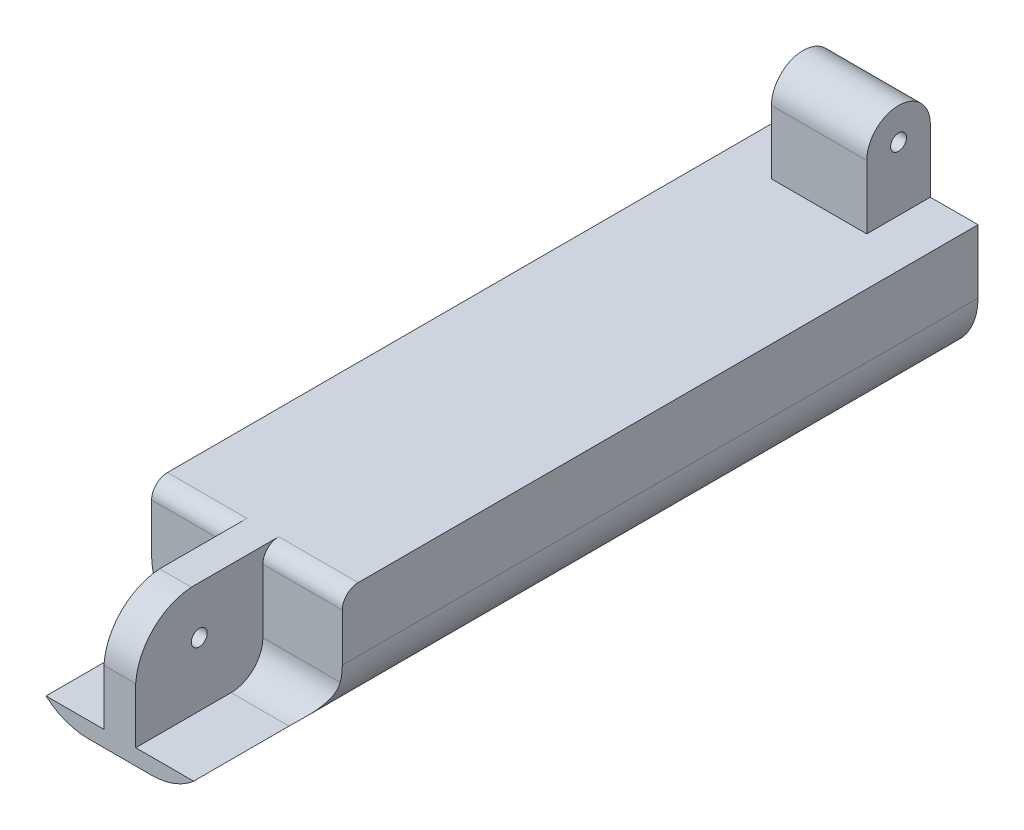
SolidWorks part; units mm, degrees
material "PVC 0.007 Plasticized"
ref_plane "Front Plane" through (0, 0, 0) normal (0, 0, 1) x (1, 0, 0)
ref_plane "Top Plane" through (0, 0, 0) normal (0, 1, 0) x (1, 0, 0)
ref_plane "Right Plane" through (0, 0, 0) normal (1, 0, 0) x (0, 0, -1)
sketch "Sketch1" plane through (0, 0, 0) normal (0, 0, 1) x (1, 0, 0)
  line L1 (0, 0) -> (-60, 0)
  line L2 (0, 0) -> (0, 40)
  line L3 (0, 40) -> (-60, 40)
  line L4 (-60, 0) -> (-60, 40)
  dimension "D1" = 60
  dimension "D2" = 40
extrude "Boss-Extrude1" add sketch "Sketch1" along normal blind 240
sketch "Sketch2" plane through (0, 40, 0) normal (0, 1, 0) x (1, 0, 0)
  line L1 (-60, -240) -> (-35, -240)
  line L2 (-60, -240) -> (-60, -200)
  line L3 (-60, -200) -> (-35, -200)
  line L4 (-35, -240) -> (-35, -200)
  line L5 (0, -240) -> (-25, -240)
  line L6 (0, -240) -> (0, -200)
  line L7 (0, -200) -> (-25, -200)
  line L8 (-25, -240) -> (-25, -200)
  dimension "D1" = 25
  dimension "D2" = 25
  dimension "D3" = 40
  dimension "D4" = 40
extrude "Cut-Extrude1" cut sketch "Sketch2" against normal blind 35
sketch "Sketch18" plane through (-25, 0, 0) normal (1, 0, 0) x (0, 0, -1)
  line L0 (-200, 5) -> (-240, 5) construction
  line L1 (-200, 5) -> (-210, 5)
  line L2 (-200, 5) -> (-200, 15)
  line L5 (-200, 5) -> (-200, 40) construction
  arc A0 (-210, 5) -> (-200, 15) centre (-210, 15) ccw
  dimension "D3" = 20
  dimension "D4" = 10
  dimension "D5" = 10
extrude "Boss-Extrude7" add sketch "Sketch18" along normal blind 25
sketch "Sketch16" plane through (-35, 0, 0) normal (-1, 0, 0) x (0, 0, 1)
  line L0 (240, 5) -> (200, 5) construction
  line L1 (200, 5) -> (200, 40) construction
  line L2 (200, 15) -> (160, 5)
  line L3 (160, 5) -> (210, 5)
  arc A0 (200, 15) -> (210, 5) centre (210, 15) ccw
  dimension "D1" = 20
  dimension "D2" = 10
  dimension "D3" = 10
extrude "Boss-Extrude5" add sketch "Sketch16" along normal blind 25
sketch "Sketch3" plane through (0, 40, 0) normal (0, 1, 0) x (1, 0, 0)
  line L0 (0, 0) -> (-60, 0) construction
  line L1 (-45, 0) -> (-15, 0)
  line L2 (-45, 0) -> (-45, -20)
  line L3 (-45, -20) -> (-15, -20)
  line L4 (-15, 0) -> (-15, -20)
  line L5 (-60, -200) -> (-60, 0) construction
  dimension "D1" = 30
  dimension "D2" = 15
  dimension "D3" = 20
extrude "Boss-Extrude2" add sketch "Sketch3" along normal blind 35
sketch "Sketch5" plane through (-25, 0, 0) normal (1, 0, 0) x (0, 0, -1)
  line L0 (-240, 5) -> (-240, 40) construction
  line L1 (-200, 40) -> (-240, 40) construction
  circle A0 centre (-220, 25) radius 2.5
  dimension "D1" = 5
  dimension "D2" = 20
  dimension "D3" = 15
extrude "Cut-Extrude3" cut sketch "Sketch5" against normal blind 30
sketch "Sketch6" plane through (0, 0, 0) normal (0, 0, -1) x (-1, 0, 0)
  line L0 (60, 40) -> (60, 0) construction
  line L1 (60, 0) -> (0, 0) construction
  line L2 (60, 20) -> (60, 0)
  line L3 (60, 0) -> (40, 0)
  line L4 (0, 0) -> (0, 40) construction
  line L5 (0, 20) -> (0, 0)
  line L6 (0, 0) -> (20, 0)
  arc A0 (60, 20) -> (40, 0) centre (40, 20) cw
  arc A1 (0, 20) -> (20, 0) centre (20, 20) ccw
extrude "Cut-Extrude4" cut sketch "Sketch6" against normal blind 240
sketch "Sketch8" plane through (-25, 0, 0) normal (1, 0, 0) x (0, 0, -1)
  line L0 (-240, 22.5) -> (-240, 40)
  line L1 (-240, 5) -> (-240, 40) construction
  line L2 (-240, 40) -> (-220, 40)
  line L3 (-200, 40) -> (-240, 40) construction
  arc A0 (-240, 22.5) -> (-220, 40) centre (-221.25, 21.25) cw
  line M3 (-240, 40) -> (-240, 5)
extrude "Cut-Extrude5" cut sketch "Sketch8" against normal blind 20 contours A0 L2 M3 region at (-25, 35.8504, 235.8504)
sketch "Sketch10" plane through (0, 0, 0) normal (1, 0, 0) x (0, 0, -1)
  line L1 (-200, 40) -> (-195, 40)
  line L2 (-200, 40) -> (-200, 35)
  arc A0 (-195, 40) -> (-200, 35) centre (-195, 35) ccw
  dimension "D3" = 10
  dimension "D5" = 5
  dimension "D4" = 5
extrude "Cut-Extrude6" cut sketch "Sketch10" against normal blind 25
sketch "Sketch11" plane through (-60, 0, 0) normal (-1, 0, 0) x (0, 0, 1)
  line L1 (200, 40) -> (195, 40)
  line L2 (200, 40) -> (200, 35)
  arc A0 (200, 35) -> (195, 40) centre (195, 35) ccw
  dimension "D3" = 10
  dimension "D5" = 5
extrude "Cut-Extrude7" cut sketch "Sketch11" against normal blind 25
sketch "Sketch19" plane through (-15, 0, 0) normal (1, 0, 0) x (0, 0, -1)
  line L0 (-20, 75) -> (-20, 40) construction
  line L1 (-20, 75) -> (0, 75) construction
  circle A0 centre (-10, 60) radius 2.5
  dimension "D1" = 5
  dimension "D2" = 10
  dimension "D3" = 15
extrude "Cut-Extrude8" cut sketch "Sketch19" against normal blind 30 contours A0
sketch "Sketch20" plane through (-15, 0, 0) normal (1, 0, 0) x (0, 0, -1)
  line L1 (-20, 75) -> (0, 75)
  line L2 (-20, 75) -> (-20, 60)
  line L4 (0, 75) -> (0, 60)
  arc A0 (0, 60) -> (-20, 60) centre (-10, 60) ccw
extrude "Cut-Extrude9" cut sketch "Sketch20" against normal blind 30
ref_axis "Axis1" through (-72.3098, 60, 10) along (1, 0, 0)
ref_axis "Axis2" through (-64.1735, 25, 220) along (1, 0, 0)
